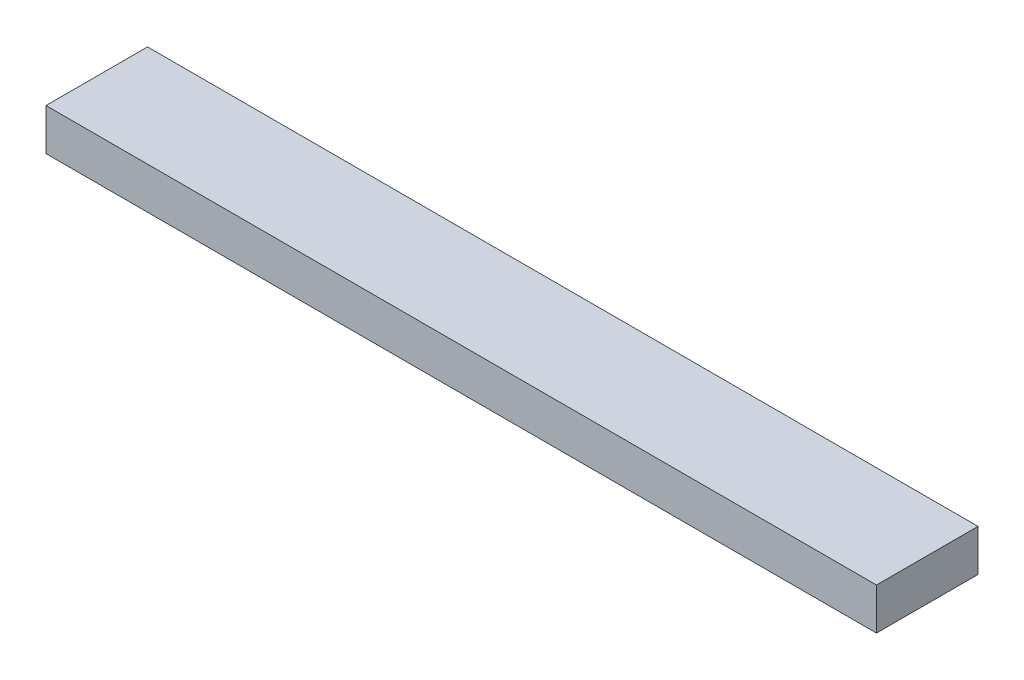
SolidWorks part; units mm, degrees
ref_plane "Спереди" through (0, 0, 0) normal (0, 0, 1) x (1, 0, 0)
ref_plane "Сверху" through (0, 0, 0) normal (0, 1, 0) x (1, 0, 0)
ref_plane "Справа" through (0, 0, 0) normal (1, 0, 0) x (0, 0, -1)
sketch "Эскиз1" plane through (0, 0, 0) normal (0, 1, 0) x (1, 0, 0)
  line L1 (31.9, -3.9) -> (-31.9, -3.9)
  line L2 (31.9, -3.9) -> (31.9, 3.9)
  line L3 (31.9, 3.9) -> (-31.9, 3.9)
  line L4 (-31.9, -3.9) -> (-31.9, 3.9)
  line L5 (31.9, -3.9) -> (-31.9, 3.9) construction
  line L6 (31.9, 3.9) -> (-31.9, -3.9) construction
  circle A0 centre (-28, 0) radius 2.5
  circle A1 centre (-20, 0) radius 2.5
  circle A2 centre (-12, 0) radius 2.5
  circle A3 centre (-4, 0) radius 2.5
  circle A4 centre (4, 0) radius 2.5
  circle A5 centre (12, 0) radius 2.5
  circle A6 centre (20, 0) radius 2.5
  circle A7 centre (28, 0) radius 2.5
  point P0 (0, 0)
  dimension "D3" = 3.9
  dimension "D6" = 5
  dimension "D1" = 7.8
  dimension "D2" = 63.8
  dimension "D4" = 3.9
  dimension "D5" = 8
extrude "Бобышка-Вытянуть2" add sketch "Эскиз1" along normal blind 3.2 contours A0 | A1 | A2 | A3 | A4 | A5 | A6 | A7 | L4 L1 L2 L3 A7 A6 A5 A4 A3 A2 A1 A0 region at (0, 0, 0) region at (-28, 0, 0) region at (-20, 0, 0) region at (-12, 0, 0) region at (-4, 0, 0) region at (4, 0, 0) region at (12, 0, 0) region at (20, 0, 0) region at (28, 0, 0)
extrude "Вырез-Вытянуть4" cut sketch "Эскиз1<7>" along normal blind 1.8 contours A2 | A3 | A5 | A6 | A7 | A1 | A0 | A4 region at (-28, 0, 0) region at (-20, 0, 0) region at (-12, 0, 0) region at (-4, 0, 0) region at (12, 0, 0) region at (20, 0, 0) region at (28, 0, 0)
sketch "Эскиз1<7>" plane through (0, 0, 0) normal (0, 1, 0) x (1, 0, 0) same geometry as "Эскиз1"
